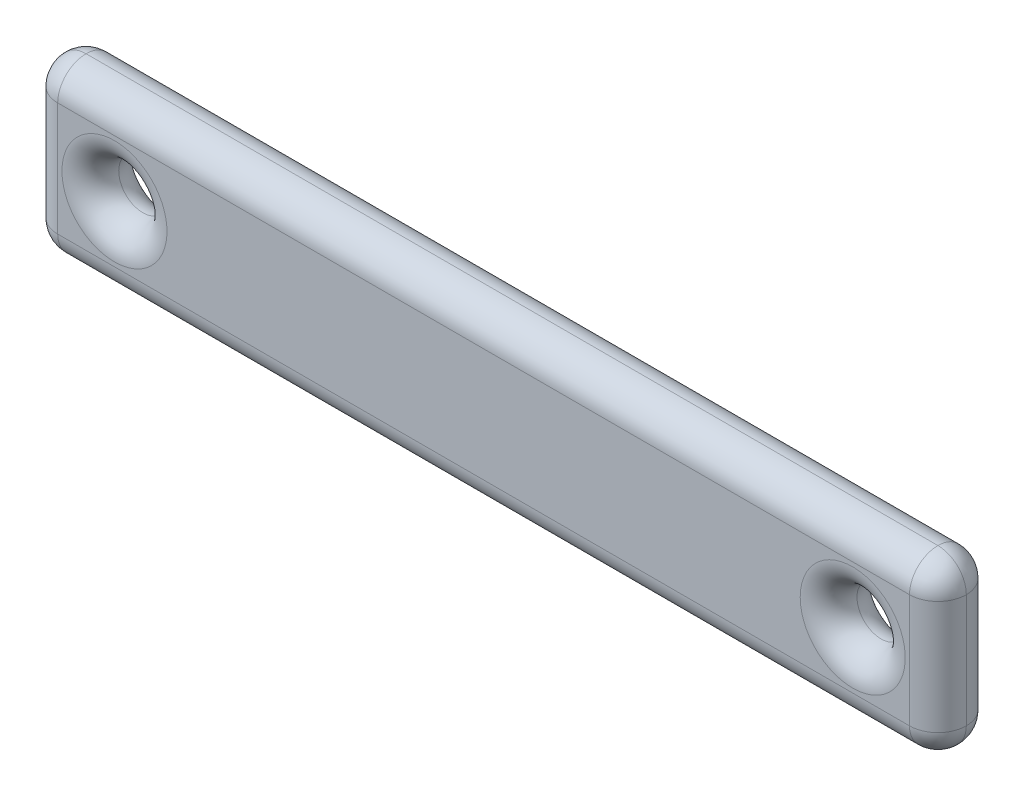
SolidWorks part; units mm, degrees
ref_plane "前视基准面" through (0, 0, 0) normal (0, 0, 1) x (1, 0, 0)
ref_plane "上视基准面" through (0, 0, 0) normal (0, 1, 0) x (1, 0, 0)
ref_plane "右视基准面" through (0, 0, 0) normal (1, 0, 0) x (0, 0, -1)
other "Configuration Table"
sketch "草图1" plane through (0, 0, 0) normal (0, 0, 1) x (1, 0, 0)
  line L1 (-6, -6) -> (58, -6)
  line L2 (-6, -6) -> (-6, 6)
  line L3 (-6, 6) -> (58, 6)
  line L4 (58, -6) -> (58, 6)
  line L5 (-6, -6) -> (58, 6) construction
  line L6 (-6, 6) -> (58, -6) construction
  circle A0 centre (0, 0) radius 1.7
  circle A1 centre (52, 0) radius 1.7
extrude "凸台-拉伸1" add sketch "草图1" along normal mid plane 4
fillet "圆角1" radius 2 12 edges at (53.7, 0, -2) (53.7, 0, 2) (1.7, 0, -2) (1.7, 0, 2) (58, 0, -2) (26, 6, -2) (-6, 0, -2) (26, -6, -2) (58, 0, 2) (26, 6, 2) (-6, 0, 2) (26, -6, 2) tangent propagation no
